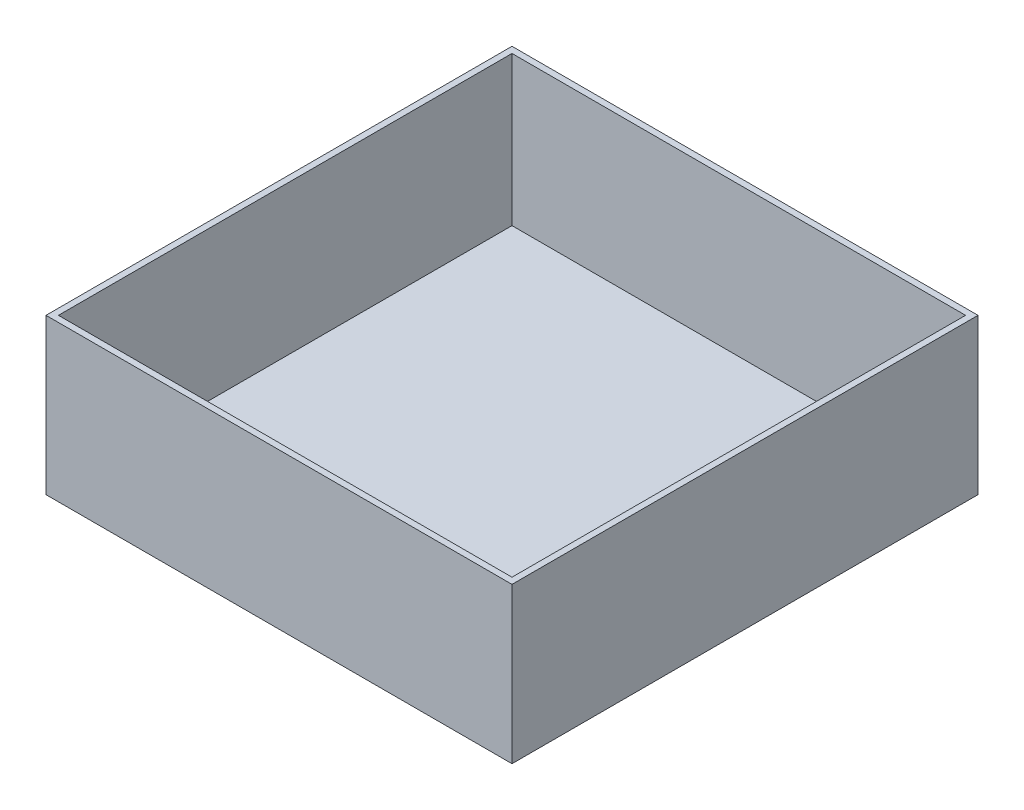
SolidWorks part; units mm, degrees
material "Aleación 1060"
ref_plane "Alzado" through (0, 0, 0) normal (0, 0, 1) x (1, 0, 0)
ref_plane "Planta" through (0, 0, 0) normal (0, 1, 0) x (1, 0, 0)
ref_plane "Vista lateral" through (0, 0, 0) normal (1, 0, 0) x (0, 0, -1)
sketch "Croquis1" plane through (0, 0, 0) normal (0, 0, 1) x (1, 0, 0)
  line L1 (-20, 20) -> (20, 20)
  line L2 (-20, 20) -> (-20, -20)
  line L3 (-20, -20) -> (20, -20)
  line L4 (20, 20) -> (20, -20)
  line L5 (-20, 20) -> (20, -20) construction
  line L6 (-20, -20) -> (20, 20) construction
  point P0 (0, 0)
  dimension "D1" = 40
  dimension "D2" = 40
extrude "Saliente-Extruir1" add sketch "Croquis1" along normal blind 0.3 contours L1 L4 L3 L2
sketch "Croquis2" plane through (0, 0, 0) normal (0, 1, 0) x (1, 0, 0)
  line L0 (0, 0) -> (0, 10) construction
  line L1 (-20, 0) -> (20, 0) construction
  line L2 (-5, 10) -> (-5, 0)
  line L3 (5, 10) -> (5, 0)
  line L4 (-5, 0) -> (5, 0)
  circle A0 centre (0, 10) radius 2.5
  arc A1 (5, 10) -> (-5, 10) centre (0, 10) ccw
  dimension "D2" = 5
  dimension "D3" = 10
  dimension "D1" = 10
extrude "Saliente-Extruir2" add sketch "Croquis2" along normal blind 10 and the other way blind 10
sketch "Croquis3" plane through (0, 0, 0) normal (0, 1, 0) x (1, 0, 0)
  line L1 (-7.0281, 16) -> (7.0281, 16)
  line L2 (-7.0281, 16) -> (-7.0281, 4)
  line L3 (-7.0281, 4) -> (7.0281, 4)
  line L4 (7.0281, 16) -> (7.0281, 4)
  line L5 (-7.0281, 16) -> (7.0281, 4) construction
  line L6 (-7.0281, 4) -> (7.0281, 16) construction
  line L7 (-20, 0) -> (20, 0) construction
  point P0 (0, 10)
  dimension "D1" = 4
extrude "Cortar-Extruir1" cut sketch "Croquis3" against normal blind 2.5 and the other way blind 2.5
sketch "Croquis4" plane through (0, 0, 0.3) normal (0, 0, 1) x (1, 0, 0)
  line L1 (-150, 50) -> (150, 50)
  line L2 (-150, 50) -> (-150, -50)
  line L3 (-150, -50) -> (150, -50)
  line L4 (150, 50) -> (150, -50)
  line L5 (-150, 50) -> (150, -50) construction
  line L6 (-150, -50) -> (150, 50) construction
  point P0 (0, 0)
  dimension "D1" = 100
  dimension "D2" = 300
extrude "Saliente-Extruir3" add sketch "Croquis4" along normal blind 300
shell "Vaciado2" thickness 4 removed face at (0, 50, 150.3)
sketch "Croquis6" plane through (0, 0, 4) normal (0, 0, 1) x (1, 0, 0)
  line L1 (16, 16) -> (-16, 16)
  line L2 (16, 16) -> (16, -16)
  line L3 (16, -16) -> (-16, -16)
  line L4 (-16, 16) -> (-16, -16)
  line L5 (16, 16) -> (-16, -16) construction
  line L6 (16, -16) -> (-16, 16) construction
  point P0 (0, 0)
extrude "Saliente-Extruir4" add sketch "Croquis6" along normal up to vertex (0.3 mm away) up to point (-16, -16, 4.3)
